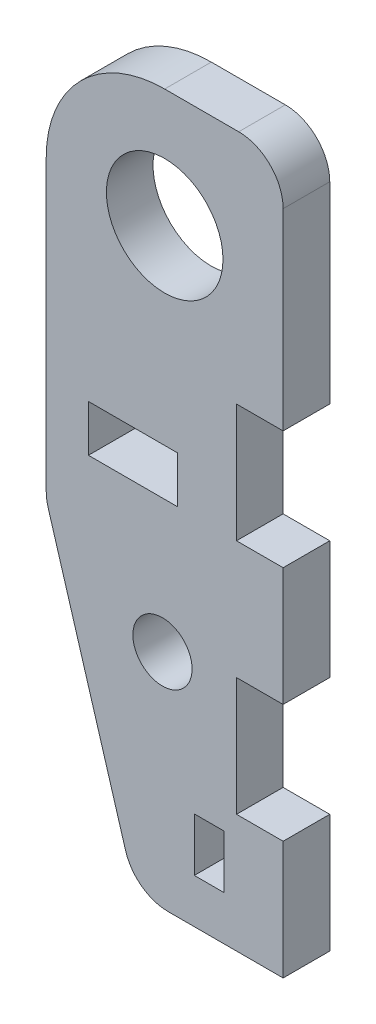
SolidWorks part; units mm, degrees
material "Hexcel AS4C (3000 Filaments)"
ref_plane "Front Plane" through (0, 0, 0) normal (0, 0, 1) x (1, 0, 0)
ref_plane "Top Plane" through (0, 0, 0) normal (0, 1, 0) x (1, 0, 0)
ref_plane "Right Plane" through (0, 0, 0) normal (1, 0, 0) x (0, 0, -1)
sketch "Sketch1" plane through (0, 0, 0) normal (0, 0, 1) x (1, 0, 0)
  line L1 (10.16, 6.35) -> (10.16, -10.16)
  line L2 (10.16, -10.16) -> (6.16, -10.16)
  line L3 (6.16, -10.16) -> (6.16, -20.32)
  line L4 (6.16, -20.32) -> (10.16, -20.32)
  line L5 (10.16, -20.32) -> (10.16, -30.48)
  line L6 (10.16, -30.48) -> (6.16, -30.48)
  line L7 (6.16, -30.48) -> (6.16, -40.64)
  line L8 (6.16, -40.64) -> (10.16, -40.64)
  line L9 (10.16, -40.64) -> (10.16, -50.8)
  line L10 (10.16, -50.8) -> (0.2948, -50.8)
  line L11 (-3.3546, -48.0848) -> (-9.9993, -25.9356)
  line L14 (0, 10.16) -> (6.35, 10.16)
  line L15 (-10.16, 0) -> (-10.16, -24.8408)
  circle A0 centre (0, 0) radius 5
  arc A2 (-10.16, 0) -> (0, 10.16) centre (0, 0) cw
  arc A3 (0.2948, -50.8) -> (-3.3546, -48.0848) centre (0.2948, -46.99) cw
  arc A4 (-9.9993, -25.9356) -> (-10.16, -24.8408) centre (-6.35, -24.8408) cw
  arc A5 (6.35, 10.16) -> (10.16, 6.35) centre (6.35, 6.35) cw
  point P20 (-2.54, -50.8)
  point P23 (-10.16, -25.4)
  dimension "D1" = 10
  dimension "D2" = 10.16
  dimension "D9" = 3.81
  dimension "D3" = 25.4
  dimension "D4" = 4
  dimension "D5" = 50.8
  dimension "D6" = 10.16
  dimension "D7" = 12.7
  dimension "D8" = 10.16
extrude "Boss-Extrude2" add sketch "Sketch1" along normal blind 4
sketch "Sketch2" plane through (0, 0, 4) normal (0, 0, 1) x (1, 0, 0)
  line L10 (0.2948, -50.8) -> (10.16, -50.8) construction
  line L11 (6.16, -40.64) -> (6.16, -30.48) construction
  circle A3 centre (-0.19, -31.75) radius 2.54
  point P0 (0, 0)
  point P18 (2.16, -45.8058)
  point P21 (2.16, -44.45)
  dimension "D6" = 5.08
  dimension "D5" = 19.05
  dimension "D7" = 6.35
extrude "Cut-Extrude1" cut sketch "Sketch2" against normal up to next
sketch "Sketch3" plane through (0, 0, 4) normal (0, 0, 1) x (1, 0, 0)
  line L1 (1.08, -16.32) -> (-6.54, -16.32)
  line L2 (1.08, -16.32) -> (1.08, -20.32)
  line L3 (1.08, -20.32) -> (-6.54, -20.32)
  line L4 (-6.54, -16.32) -> (-6.54, -20.32)
  line L6 (6.16, -20.32) -> (6.16, -10.16) construction
  line L7 (10.16, -20.32) -> (6.16, -20.32) construction
  dimension "D1" = 7.62
  dimension "D2" = 5.08
  dimension "D3" = 4
extrude "Cut-Extrude2" cut sketch "Sketch3" against normal through all
sketch "Sketch4" plane through (0, 0, 4) normal (0, 0, 1) x (1, 0, 0)
  line L0 (0.2948, -50.8) -> (10.16, -50.8) construction
  line L1 (5.08, -42.418) -> (2.54, -42.418)
  line L2 (5.08, -42.418) -> (5.08, -46.99)
  line L3 (5.08, -46.99) -> (2.54, -46.99)
  line L4 (2.54, -42.418) -> (2.54, -46.99)
  line L5 (10.16, -50.8) -> (10.16, -40.64) construction
  dimension "D1" = 2.54
  dimension "D2" = 4.572
  dimension "D3" = 3.81
  dimension "D4" = 5.08
extrude "Cut-Extrude3" cut sketch "Sketch4" against normal up to surface (4 mm away) up to face at (-2.73, -18.32, 0)
